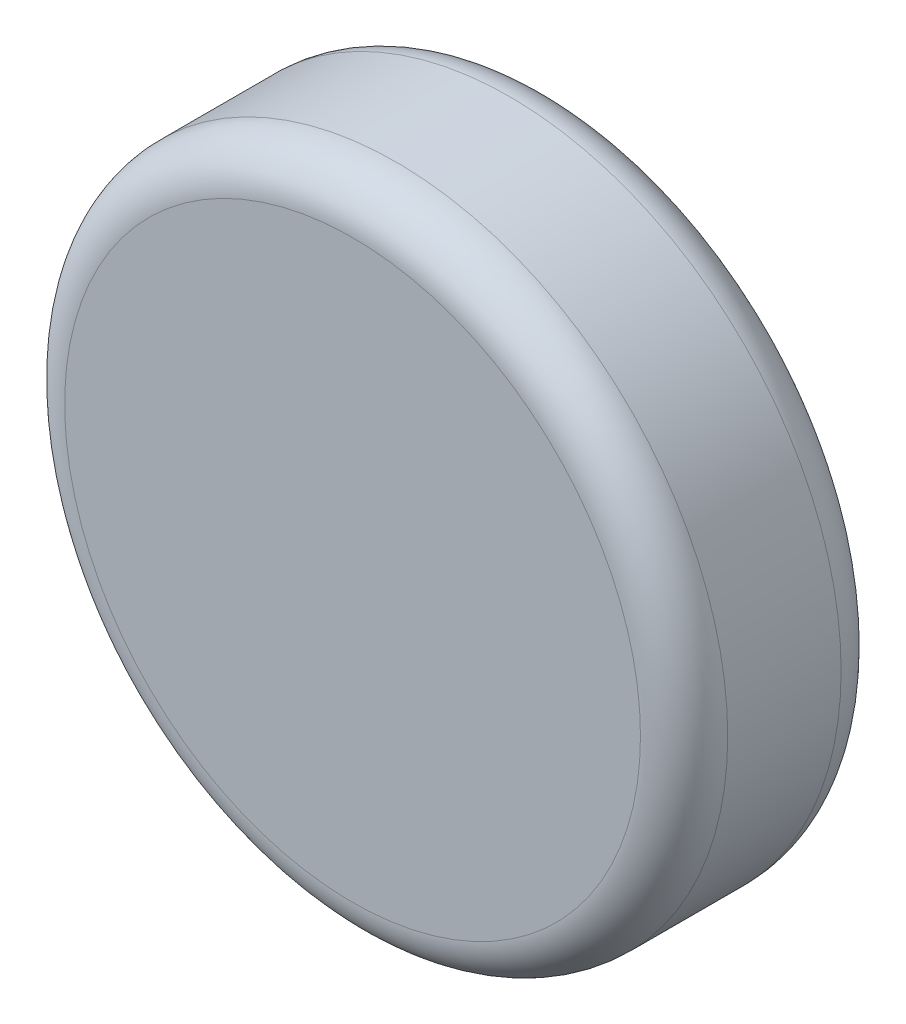
SolidWorks part; units mm, degrees
ref_plane "正面" through (0, 0, 0) normal (0, 0, 1) x (1, 0, 0)
ref_plane "平面" through (0, 0, 0) normal (0, 1, 0) x (1, 0, 0)
ref_plane "右側面" through (0, 0, 0) normal (1, 0, 0) x (0, 0, -1)
sketch "ｽｹｯﾁ2" plane through (0, 0, 0) normal (0, 0, 1) x (1, 0, 0)
  circle A0 centre (0, 0) radius 76
  dimension "D1" = 152
extrude "ﾎﾞｽ - 押し出し2" add sketch "ｽｹｯﾁ2" along normal blind 46
fillet "ﾌｨﾚｯﾄ1" radius 10 2 edges at (76, 0, 46) (76, 0, 0)
